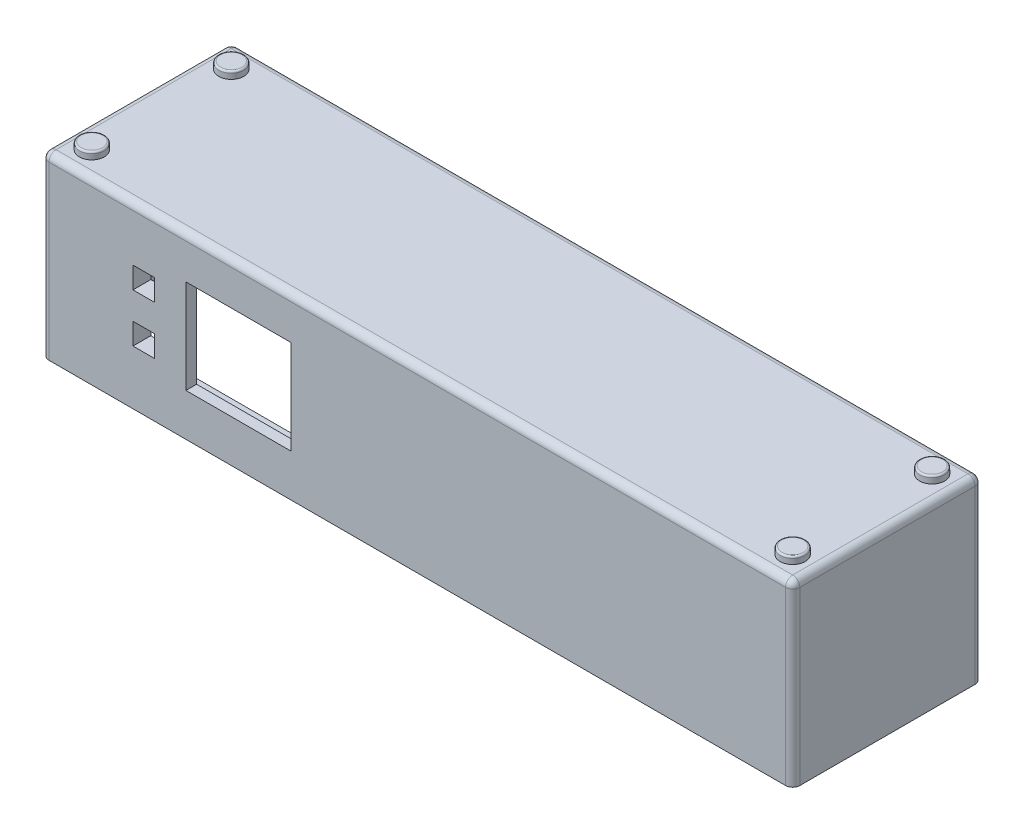
SolidWorks part; units mm, degrees
material "PET"
ref_plane "Спереди" through (0, 0, 0) normal (0, 0, 1) x (1, 0, 0)
ref_plane "Сверху" through (0, 0, 0) normal (0, 1, 0) x (1, 0, 0)
ref_plane "Справа" through (0, 0, 0) normal (1, 0, 0) x (0, 0, -1)
other "Configuration Table"
sketch "Основание & крышка" plane through (0, 0, 0) normal (0, 1, 0) x (1, 0, 0)
  line L1 (105, -26.5) -> (-105, -26.5)
  line L2 (105, -26.5) -> (105, 26.5)
  line L3 (105, 26.5) -> (-105, 26.5)
  line L4 (-105, -26.5) -> (-105, 26.5)
  line L5 (105, -26.5) -> (-105, 26.5) construction
  line L6 (105, 26.5) -> (-105, -26.5) construction
  line L7 (100, -21.5) -> (-100, -21.5)
  line L8 (100, -21.5) -> (100, 21.5)
  line L9 (100, 21.5) -> (-100, 21.5)
  line L10 (-100, -21.5) -> (-100, 21.5)
  line L11 (100, -21.5) -> (-100, 21.5) construction
  line L12 (100, 21.5) -> (-100, -21.5) construction
  point P0 (0, 0)
  point P5 (0, 0)
  dimension "D1" = 210
  dimension "D2" = 53
  dimension "D3" = 43
  dimension "D4" = 200
extrude "Бобышка-Вытянуть1" add sketch "Основание & крышка" along normal blind 50 contours L3 L4 L1 L2
sketch "Эскиз3" plane through (0, 0, 0) normal (0, -1, 0) x (1, 0, 0)
  line L0 (105, 26.5) -> (-105, 26.5) construction
  line L1 (-100, -21.5) -> (100, -21.5)
  line L2 (-100, -21.5) -> (-100, 21.5)
  line L3 (-100, 21.5) -> (100, 21.5)
  line L4 (100, -21.5) -> (100, 21.5)
  line L5 (-100, -21.5) -> (100, 21.5) construction
  line L6 (-100, 21.5) -> (100, -21.5) construction
  line L7 (105, 26.5) -> (105, -26.5) construction
  point P0 (0, 0)
  dimension "D1" = 5
  dimension "D2" = 5
extrude "Вырез-Вытянуть1" cut sketch "Эскиз3" against normal blind 45
sketch "Эскиз4" plane through (0, 50, 0) normal (0, 1, 0) x (1, 0, 0)
  line L0 (0, 41.131) -> (0, -55.5904) construction
  line L1 (105, 26.5) -> (-105, 26.5) construction
  line L2 (105, -26.5) -> (105, 26.5) construction
  line L3 (-127.2033, 0) -> (126.8125, 0) construction
  circle A0 centre (98, 19.5) radius 3.5
  circle A1 centre (-98, 19.5) radius 3.5
  circle A2 centre (98, -19.5) radius 3.5
  circle A3 centre (-98, -19.5) radius 3.5
  dimension "D1" = 7
  dimension "D3" = 7
  dimension "D2" = 7
sketch "Эскиз6" plane through (0, 50, 0) normal (0, 1, 0) x (1, 0, 0)
  line L0 (-117.6289, 0) -> (122.9046, 0) construction
  line L1 (0, 47.7745) -> (0, -57.5444) construction
extrude "Бобышка-Вытянуть2" add sketch "Эскиз4" along normal blind 2 draft 1 contours A0
fillet "Скругление2" radius 0.5 1 edges at (98, 52, -16.0349)
extrude "Бобышка-Вытянуть3" add sketch "Эскиз4<5>" along normal blind 2 contours A2
sketch "Эскиз4<5>" plane through (0, 50, 0) normal (0, 1, 0) x (1, 0, 0) same geometry as "Эскиз4"
extrude "Бобышка-Вытянуть4" add sketch "Эскиз4<6>" along normal blind 2 contours A3
sketch "Эскиз4<6>" plane through (0, 50, 0) normal (0, 1, 0) x (1, 0, 0) same geometry as "Эскиз4"
extrude "Бобышка-Вытянуть5" add sketch "Эскиз4<7>" along normal blind 2 contours A1
sketch "Эскиз4<7>" plane through (0, 50, 0) normal (0, 1, 0) x (1, 0, 0) same geometry as "Эскиз4"
fillet "Скругление3" radius 0.5 1 edges at (-98, 52, 23)
fillet "Скругление4" radius 0.5 1 edges at (-98, 52, -23)
fillet "Скругление5" radius 0.5 1 edges at (98, 52, 16)
sketch "Эскиз7" plane through (0, 0, -26.5) normal (0, 0, -1) x (-1, 0, 0)
  line L0 (0, -32.9698) -> (0, 82.1336) construction
  line L1 (-136.416, 24.5819) -> (136.5704, 24.5819) construction
  circle A0 centre (0, 35.0819) radius 6
  point P7 (0, 24.5819)
  dimension "D1" = 12
  dimension "D2" = 10.5
extrude "Вырез-Вытянуть2" cut sketch "Эскиз7" against normal blind 14 draft 5 contours A0
fillet "Скругление6" radius 2 1 edges at (-6, 35.0819, -26.5)
sketch "Эскиз8" plane through (0, 0, -21.5) normal (0, 0, 1) x (1, 0, 0)
  circle A0 centre (0, 35.0819) radius 7
  dimension "D1" = 14
extrude "Бобышка-Вытянуть6" add sketch "Эскиз8" along normal blind 7 draft 5 contours A0
sketch "Эскиз9" plane through (0, 0, -14.5) normal (0, 0, 1) x (1, 0, 0)
  circle A0 centre (0, 35.0819) radius 5.15
  dimension "D1" = 10.3
extrude "Вырез-Вытянуть3" cut sketch "Эскиз9" against normal blind 7 draft 5 draft outward yes
sketch "Эскиз10" plane through (0, 0, 26.5) normal (0, 0, 1) x (1, 0, 0)
  line L0 (0, -14.7722) -> (0, 61.6389) construction
  line L1 (-118.5615, 25) -> (116.6086, 25) construction
  line L2 (-127.2033, 50) -> (126.8125, 50) construction
  line L3 (-64.7, 38.15) -> (-35.3, 38.15)
  line L4 (-64.7, 38.15) -> (-64.7, 11.85)
  line L5 (-64.7, 11.85) -> (-35.3, 11.85)
  line L6 (-35.3, 38.15) -> (-35.3, 11.85)
  line L7 (-64.7, 38.15) -> (-35.3, 11.85) construction
  line L8 (-64.7, 11.85) -> (-35.3, 38.15) construction
  point P5 (-50, 25)
  point P13 (0, 25)
  dimension "D1" = 29.4
  dimension "D2" = 26.3
  dimension "D3" = 50
  dimension "D4" = 25
extrude "Вырез-Вытянуть4" cut sketch "Эскиз10" against normal blind 5
sketch "Эскиз13" plane through (0, 0, 21.5) normal (0, 0, -1) x (-1, 0, 0)
  line L0 (100, 45) -> (100, 0) construction
  line L1 (30.4, 38.75) -> (69.6, 38.75)
  line L2 (30.4, 38.75) -> (30.4, 11.25)
  line L3 (30.4, 11.25) -> (69.6, 11.25)
  line L4 (69.6, 38.75) -> (69.6, 11.25)
  line L5 (30.4, 38.75) -> (69.6, 11.25) construction
  line L6 (30.4, 11.25) -> (69.6, 38.75) construction
  line L8 (-100, 45) -> (100, 45) construction
  point P0 (50, 25)
  dimension "D1" = 50
  dimension "D2" = 20
  dimension "D3" = 27.5
  dimension "D4" = 39.2
extrude "Вырез-Вытянуть5" cut sketch "Эскиз13" against normal blind 2
sketch "Эскиз14" plane through (0, 0, 26.5) normal (0, 0, 1) x (1, 0, 0)
  line L0 (0, 0) -> (0, 50) construction
  line L1 (105, 0) -> (-105, 0) construction
  line L2 (105, 50) -> (-105, 50) construction
  line L3 (-105, 25) -> (105, 25) construction
  line L4 (-105, 50) -> (-105, 0) construction
  line L5 (105, 50) -> (105, 0) construction
  line L6 (-79.5, 28.8) -> (-73.5, 28.8)
  line L7 (-79.5, 15.2) -> (-73.5, 15.2)
  line L8 (-79.5, 15.2) -> (-79.5, 21.2)
  line L9 (-79.5, 21.2) -> (-73.5, 21.2)
  line L10 (-73.5, 15.2) -> (-73.5, 21.2)
  line L11 (-79.5, 15.2) -> (-73.5, 21.2) construction
  line L12 (-79.5, 21.2) -> (-73.5, 15.2) construction
  line L13 (-79.5, 28.8) -> (-73.5, 34.8) construction
  line L14 (-79.5, 34.8) -> (-79.5, 28.8)
  line L15 (-79.5, 34.8) -> (-73.5, 28.8) construction
  line L16 (-73.5, 34.8) -> (-73.5, 28.8)
  line L17 (-79.5, 34.8) -> (-73.5, 34.8)
  point P12 (-76.5, 18.2)
  point P21 (-76.5, 31.8)
  dimension "D1" = 6
  dimension "D2" = 6
  dimension "D3" = 18.2
  dimension "D4" = 25.5
extrude "Вырез-Вытянуть6" cut sketch "Эскиз14" against normal blind 5
sketch "Эскиз16" plane through (0, 0, 21.5) normal (0, 0, -1) x (-1, 0, 0)
  line L0 (-100, 45) -> (100, 45) construction
  line L1 (73.4, 34.85) -> (79.5, 34.85)
  line L2 (73.4, 34.85) -> (73.4, 28.75)
  line L3 (73.4, 28.75) -> (79.5, 28.75)
  line L4 (79.5, 34.85) -> (79.5, 28.75)
  line L5 (73.4, 34.85) -> (79.5, 28.75) construction
  line L6 (73.4, 28.75) -> (79.5, 34.85) construction
  line L7 (100, 45) -> (100, 0) construction
  point P0 (76.45, 31.8)
  dimension "D1" = 6.1
  dimension "D2" = 6.1
  dimension "D3" = 13.2
  dimension "D4" = 20.5
fillet "Скругление7" radius 2 8 edges at (-105, 25, -26.5) (-105, 50, 0) (0, 50, -26.5) (105, 25, -26.5) (105, 50, 0) (105, 25, 26.5) (-105, 25, 26.5) (0, 50, 26.5)
sketch "Эскиз17" plane through (0, 0, 0) normal (0, -1, 0) x (1, 0, 0)
  line L4 (-105, 24.5) -> (-105, -24.5)
  line L5 (-103, -26.5) -> (103, -26.5)
  line L6 (105, -24.5) -> (105, 24.5)
  line L7 (103, 26.5) -> (-103, 26.5)
  line L8 (-105, 24.5) -> (-105, -24.5)
  line L9 (-103, -26.5) -> (103, -26.5)
  line L10 (105, -24.5) -> (105, 24.5)
  line L11 (103, 26.5) -> (-103, 26.5)
  arc A4 (-105, -24.5) -> (-103, -26.5) centre (-103, -24.5) ccw
  arc A5 (103, -26.5) -> (105, -24.5) centre (103, -24.5) ccw
  arc A6 (105, 24.5) -> (103, 26.5) centre (103, 24.5) ccw
  arc A7 (-103, 26.5) -> (-105, 24.5) centre (-103, 24.5) ccw
  arc A8 (-105, -24.5) -> (-103, -26.5) centre (-103, -24.5) ccw
  arc A9 (103, -26.5) -> (105, -24.5) centre (103, -24.5) ccw
  arc A10 (105, 24.5) -> (103, 26.5) centre (103, 24.5) ccw
  arc A11 (-103, 26.5) -> (-105, 24.5) centre (-103, 24.5) ccw
  dimension "D1" = 0
extrude "Бобышка-Вытянуть8" add sketch "Эскиз17" along normal blind 3 separate body
sketch "Эскиз18" plane through (0, 0, 0) normal (0, 1, 0) x (1, 0, 0)
  line L8 (-100, -21.5) -> (100, -21.5)
  line L28 (-100, -21.5) -> (100, -21.5)
  line L32 (100, -21.5) -> (100, 21.5)
  line L34 (100, -21.5) -> (100, 21.5)
  line L36 (100, 21.5) -> (-100, 21.5)
  line L37 (100, 21.5) -> (-100, 21.5)
  line L38 (-100, 21.5) -> (-100, -21.5)
  line L39 (-100, 21.5) -> (-100, -21.5)
  dimension "D1" = 5
extrude "Крышка" add sketch "Эскиз18" along normal blind 3 from surface thin contours L37 L39 L28 L34 starting at face at (0, 0, 0) thin type one direction reverse wall 3
sketch "Эскиз20" plane through (0, -3, 0) normal (0, -1, 0) x (1, 0, 0)
  line L0 (-105, 0) -> (105, 0) construction
  line L1 (-105, 24.5) -> (-105, -24.5) construction
  line L2 (105, -24.5) -> (105, 24.5) construction
  line L3 (0, 26.5) -> (0, -26.5) construction
  line L4 (103, 26.5) -> (-103, 26.5) construction
  line L5 (-103, -26.5) -> (103, -26.5) construction
sketch "Эскиз21" plane through (0, -3, 0) normal (0, -1, 0) x (1, 0, 0)
  line L0 (-66.7, -49.4791) -> (-66.7, 41.6381) construction
  line L1 (-33.4, -45.2678) -> (-33.4, 45.8494) construction
  line L2 (33.4, -44.7574) -> (33.4, 46.3598) construction
  line L3 (66.7, -45.7783) -> (66.7, 45.3389) construction
  line L4 (105, -24.5) -> (105, 24.5) construction
  line L5 (0, 26.5) -> (0, -26.5) construction
  line L6 (0, -41.131) -> (0, 55.5904) construction
  line L7 (15.5, 60.8548) -> (15.5, -34.3859) construction
  line L8 (10.5, 21.5) -> (20.5, 21.5)
  line L9 (10.5, 21.5) -> (10.5, 19.5)
  line L10 (10.5, 19.5) -> (20.5, 19.5)
  line L11 (20.5, 21.5) -> (20.5, 19.5)
  line L12 (10.5, 21.5) -> (20.5, 19.5) construction
  line L13 (10.5, 19.5) -> (20.5, 21.5) construction
  line L26 (103, 26.5) -> (-103, 26.5) construction
  line L27 (-10.5, 19.5) -> (-20.5, 21.5) construction
  line L28 (-10.5, 21.5) -> (-20.5, 19.5) construction
  line L33 (-20.5, 21.5) -> (-20.5, 19.5)
  line L34 (-10.5, 19.5) -> (-20.5, 19.5)
  line L39 (-10.5, 21.5) -> (-10.5, 19.5)
  line L40 (-10.5, 21.5) -> (-20.5, 21.5)
  line L45 (-56.3, 21.5) -> (-46.3, 19.5) construction
  line L46 (-56.3, 19.5) -> (-46.3, 21.5) construction
  line L51 (-56.3, 21.5) -> (-46.3, 21.5)
  line L52 (-56.3, 21.5) -> (-56.3, 19.5)
  line L57 (-56.3, 19.5) -> (-46.3, 19.5)
  line L58 (-46.3, 21.5) -> (-46.3, 19.5)
  line L63 (-77.1, 19.5) -> (-87.1, 21.5) construction
  line L64 (-77.1, 21.5) -> (-87.1, 19.5) construction
  line L69 (-87.1, 21.5) -> (-87.1, 19.5)
  line L70 (-77.1, 19.5) -> (-87.1, 19.5)
  line L75 (-77.1, 21.5) -> (-77.1, 19.5)
  line L76 (-77.1, 21.5) -> (-87.1, 21.5)
  line L78 (77.3, 21.5) -> (87.3, 19.5) construction
  line L79 (77.3, 19.5) -> (87.3, 21.5) construction
  line L80 (56.3, 19.5) -> (46.3, 21.5) construction
  line L81 (56.3, 21.5) -> (46.3, 19.5) construction
  line L82 (77.3, 21.5) -> (87.3, 21.5)
  line L83 (77.3, 21.5) -> (77.3, 19.5)
  line L84 (77.3, 19.5) -> (87.3, 19.5)
  line L85 (87.3, 21.5) -> (87.3, 19.5)
  line L86 (46.3, 21.5) -> (46.3, 19.5)
  line L87 (56.3, 19.5) -> (46.3, 19.5)
  line L88 (56.3, 21.5) -> (56.3, 19.5)
  line L89 (56.3, 21.5) -> (46.3, 21.5)
  line L198 (0, 55.5904) -> (0, -41.131) construction
  point P14 (15.5, 20.5)
  point P23 (-15.5, 20.5)
  point P28 (-51.3, 20.5)
  point P31 (15.5, 21.5)
  point P38 (-82.1, 20.5)
  point P47 (82.3, 20.5)
  point P48 (51.3, 20.5)
  dimension "D1" = 38.3
  dimension "D2" = 33.3
  dimension "D3" = 33.4
  dimension "D4" = 33.4
  dimension "D5" = 33.3
  dimension "D6" = 15.5
  dimension "D7" = 10
  dimension "D8" = 2
  dimension "D9" = 5
extrude "Вырез-Вытянуть12" cut sketch "Эскиз21" against normal blind 5
pattern_linear "Линейный массив1" count 10 spacing 4.5 along (0, 0, -1) of "Вырез-Вытянуть12"
delete or keep bodies "Тело-Удалить/Сохранить 2" type keep bodies bodies 114
